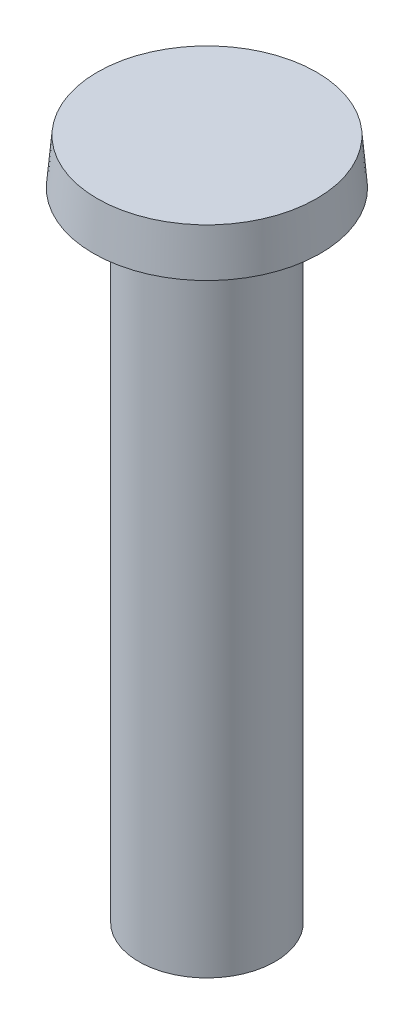
SolidWorks part; units mm, degrees
ref_plane "Front Plane" through (0, 0, 0) normal (0, 0, 1) x (1, 0, 0)
ref_plane "Top Plane" through (0, 0, 0) normal (0, 1, 0) x (1, 0, 0)
ref_plane "Right Plane" through (0, 0, 0) normal (1, 0, 0) x (0, 0, -1)
sketch "Sketch1" plane through (0, 0, 0) normal (0, 1, 0) x (1, 0, 0)
  circle A0 centre (0, 0) radius 2.25
  dimension "D1" = 4.5
extrude "Boss-Extrude1" add sketch "Sketch1" along normal blind 21
sketch "Sketch2" plane through (0, 21, 0) normal (0, 1, 0) x (1, 0, 0)
  circle A0 centre (0, 0) radius 3.75
  circle A1 centre (0, 0) radius 2.25 construction
  dimension "D1" = 1.5
extrude "Boss-Extrude2" add sketch "Sketch2" along normal blind 1.5 draft 5
sketch "Sketch3" plane through (0, 0, 0) normal (0, -1, 0) x (1, 0, 0)
  circle A0 centre (0, 0) radius 0.75
  dimension "D1" = 1.5
extrude "Cut-Extrude1" cut sketch "Sketch3" against normal blind 4 draft 5
